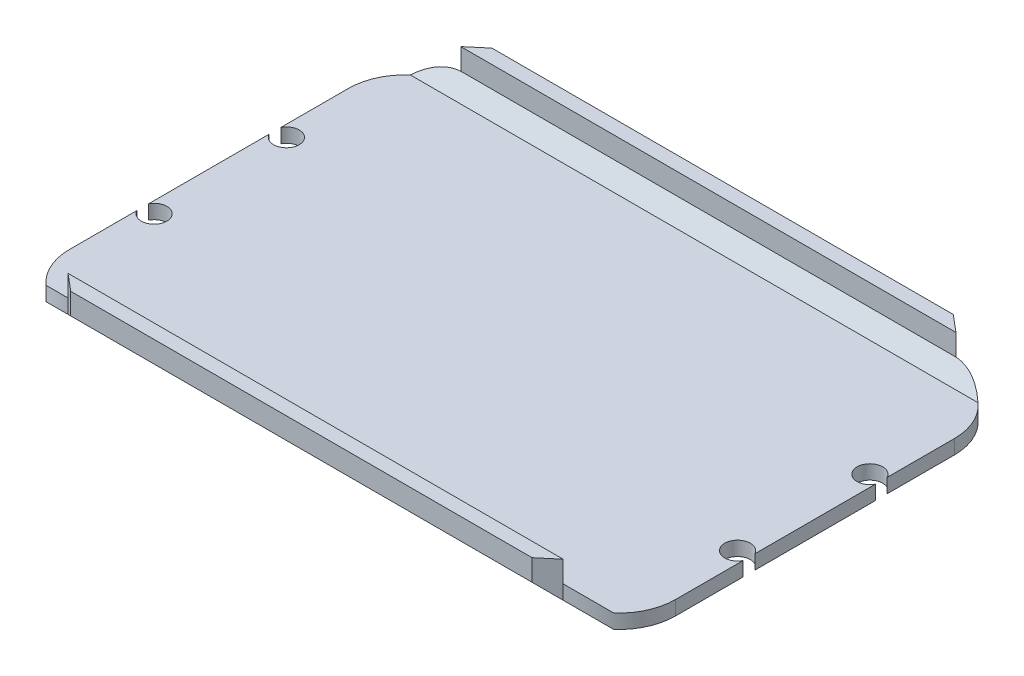
SolidWorks part; units mm, degrees
ref_plane "前视基准面" through (0, 0, 0) normal (0, 0, 1) x (1, 0, 0)
ref_plane "上视基准面" through (0, 0, 0) normal (0, 1, 0) x (1, 0, 0)
ref_plane "右视基准面" through (0, 0, 0) normal (1, 0, 0) x (0, 0, -1)
sketch "草图1" plane through (0, 0, 0) normal (0, 1, 0) x (1, 0, 0)
  line L1 (-21.3, 13.8) -> (21.3, 13.8)
  line L2 (-21.3, 13.8) -> (-21.3, -13.8)
  line L3 (-21.3, -13.8) -> (21.3, -13.8)
  line L4 (21.3, 13.8) -> (21.3, -13.8)
  line L5 (-21.3, 13.8) -> (21.3, -13.8) construction
  line L6 (-21.3, -13.8) -> (21.3, 13.8) construction
  point P0 (0, 0)
  dimension "D1" = 42.6
  dimension "D2" = 27.6
extrude "凸台-拉伸1" add sketch "草图1" along normal blind 1
fillet "圆角1" radius 4 4 edges at (21.3, 0.5, -13.8) (-21.3, 0.5, -13.8) (-21.3, 0.5, 13.8) (21.3, 0.5, 13.8)
sketch "草图2" plane through (0, 1, 0) normal (0, 1, 0) x (1, 0, 0)
  line L0 (0, -13.8) -> (0, 13.8) construction
  line L1 (-17.3, -13.8) -> (17.3, -13.8) construction
  line L2 (17.3, 13.8) -> (-17.3, 13.8) construction
  line L3 (17.4, -13.8) -> (16.2082, -14.8)
  line L4 (16.2082, -14.8) -> (-16.2082, -14.8)
  line L5 (17.4, -13.8) -> (-17.4, -13.8)
  line L6 (-17.4, -13.8) -> (-16.2082, -14.8)
  line L7 (21.3, 0) -> (-21.3, 0) construction
  line L8 (21.3, -9.8) -> (21.3, 9.8) construction
  line L9 (-21.3, 9.8) -> (-21.3, -9.8) construction
  line L10 (-17.4, 13.8) -> (-16.2082, 14.8)
  line L11 (17.4, 13.8) -> (-17.4, 13.8)
  line L12 (16.2082, 14.8) -> (-16.2082, 14.8)
  line L13 (17.4, 13.8) -> (16.2082, 14.8)
  point P11 (0, -14.8)
  point P21 (0, 14.8)
  dimension "D1" = 17.4
  dimension "D2" = 1
extrude "凸台-拉伸2" add sketch "草图2" along normal blind 2.5 and the other way blind 1
chamfer "倒角1" distance 2 angle 45 2 edges at (0, 0, 14.8) (0, 0, -14.8)
chamfer "倒角3" distance 1 angle 45 2 edges at (0, 1, -13.8) (0, 1, 13.8)
sketch "草图3" plane through (0, 0, 0) normal (0, -1, 0) x (1, 0, 0)
  line L0 (-21.3, 0) -> (21.3, 0) construction
  line L1 (-21.3, -9.8) -> (-21.3, 9.8) construction
  line L2 (21.3, 9.8) -> (21.3, -9.8) construction
  line L3 (0, 12.8) -> (0, -12.8) construction
  line L4 (19.9458, 12.8) -> (-19.9458, 12.8) construction
  line L5 (-19.9458, -12.8) -> (19.9458, -12.8) construction
  circle A0 centre (-20.5, 4.65) radius 0.9
  circle A1 centre (-20.5, -4.65) radius 0.9
  circle A2 centre (20.5, -4.65) radius 0.9
  circle A3 centre (20.5, 4.65) radius 0.9
  dimension "D3" = 1.8
  dimension "D1" = 0.8
  dimension "D2" = 4.65
extrude "切除-拉伸1" cut sketch "草图3" against normal up to next
